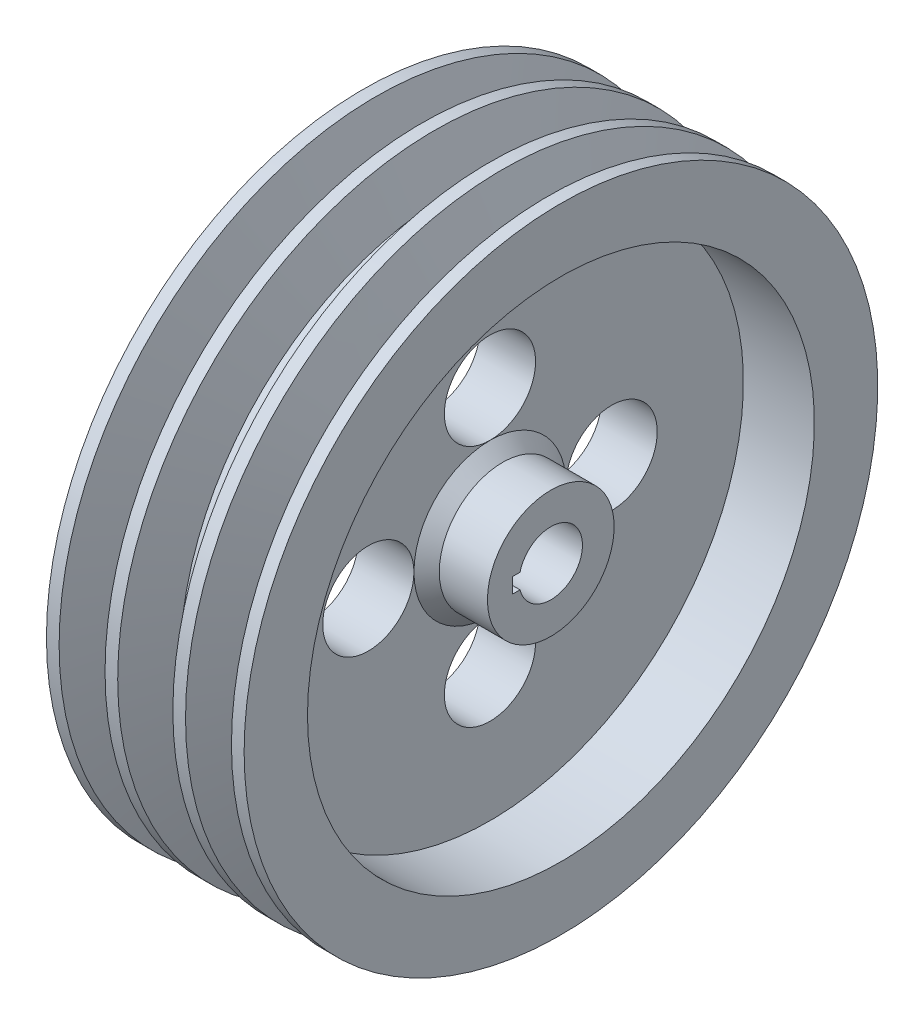
SolidWorks part; units mm, degrees
ref_plane "Front Plane" through (0, 0, 0) normal (0, 0, 1) x (1, 0, 0)
ref_plane "Top Plane" through (0, 0, 0) normal (0, 1, 0) x (1, 0, 0)
ref_plane "Right Plane" through (0, 0, 0) normal (1, 0, 0) x (0, 0, -1)
sketch "Sketch1" plane through (0, 0, 0) normal (0, 0, 1) x (1, 0, 0)
  line L0 (-68.9141, 0) -> (82.743, 0) construction
  line L3 (35, 25) -> (16, 25)
  line L4 (11, 30) -> (11, 39.2865)
  line L6 (-11, 39.2865) -> (-11, 30)
  line L7 (-16, 25) -> (-30, 25)
  line L9 (-35, 20) -> (-35, 12.5)
  line L10 (-35, 12.5) -> (35, 12.5)
  line L11 (35, 12.5) -> (35, 25)
  line L13 (0, -10.9907) -> (0, 170.2556) construction
  line L14 (-11, 30) -> (-16, 25)
  line L15 (16, 25) -> (11, 30)
  line L17 (11, 75.2865) -> (11, 100)
  line L18 (11, 100) -> (39, 100)
  line L19 (39, 100) -> (39, 125)
  line L20 (39, 125) -> (34, 125)
  line L21 (34, 125) -> (28.1327, 107)
  line L22 (28.1327, 107) -> (23.1327, 107)
  line L23 (23.1327, 107) -> (15.8799, 125)
  line L28 (4.3285, 107) -> (-4.3285, 107)
  line L30 (15.8799, 125) -> (10.8799, 125)
  line L32 (10.8799, 125) -> (4.3285, 107)
  line L33 (-11, 75.2865) -> (-11, 100)
  line L34 (-11, 100) -> (-39, 100)
  line L35 (-39, 100) -> (-39, 125)
  line L36 (-39, 125) -> (-34, 125)
  line L37 (-15.8799, 125) -> (-10.8799, 125)
  line L38 (-34, 125) -> (-28.1327, 107)
  line L39 (-23.1327, 107) -> (-15.8799, 125)
  line L40 (-10.8799, 125) -> (-4.3285, 107)
  line L41 (-28.1327, 107) -> (-23.1327, 107)
  line L42 (-11, 75.2865) -> (-11, 39.2865)
  line L43 (11, 75.2865) -> (11, 39.2865)
  arc A0 (-30, 25) -> (-35, 20) centre (-30, 20) ccw
  point P7 (11, 25)
  point P10 (-11, 25)
  point P40 (0, 107)
  dimension "D15" = 20
  dimension "D16" = 5
  dimension "D17" = 39
  dimension "D6" = 5
  dimension "D1" = 12.5
  dimension "D2" = 25
  dimension "D3" = 25
  dimension "D4" = 22
  dimension "D5" = 70
  dimension "D7" = 36
  dimension "D8" = 36
  dimension "D11" = 25
  dimension "D12" = 18
  dimension "D13" = 40
  dimension "D14" = 5
  dimension "D18" = 5
  dimension "D19" = 22
  dimension "D20" = 8.6569
  dimension "D21" = 125
  dimension "D22" = 9.2865
revolve "Revolve9" add sketch "Sketch1" angle 360 about L0
sketch "Sketch2" plane through (-11, 0, 0) normal (-1, 0, 0) x (0, 0, 1)
  line L0 (0, 134.4605) -> (0, -150.5498) construction
  line L1 (-146.5275, 0) -> (150.3583, 0) construction
  circle A0 centre (0, 48) radius 18
  circle A1 centre (48, 0) radius 18
  circle A2 centre (0, 0) radius 30 construction
  circle A3 centre (0, -48) radius 18
  circle A4 centre (-48, 0) radius 18
  point P18 (0, 0)
  dimension "D1" = 36
  dimension "D4" = 150.3583
  dimension "D5" = 146.5275
  dimension "D6" = 134.4605
  dimension "D7" = 150.5498
  dimension "D2" = 4
extrude "Cut-Extrude1" cut sketch "Sketch2" against normal through all and the other way through all
sketch "Sketch3" plane through (-35, 0, 0) normal (-1, 0, 0) x (0, 0, 1)
  line L0 (0, 0) -> (15.1347, 0) construction
  line L1 (12.1347, 3) -> (15.1347, 3)
  line L2 (15.1347, 3) -> (15.1347, -3)
  line L3 (15.1347, -3) -> (12.1347, -3)
  circle A0 centre (0, 0) radius 12.5 construction
  arc A1 (12.1347, 3) -> (12.1347, -3) centre (0, 0) ccw
  dimension "D1" = 6
  dimension "D2" = 3
  dimension "D3" = 3
extrude "Cut-Extrude2" cut sketch "Sketch3" against normal through all
